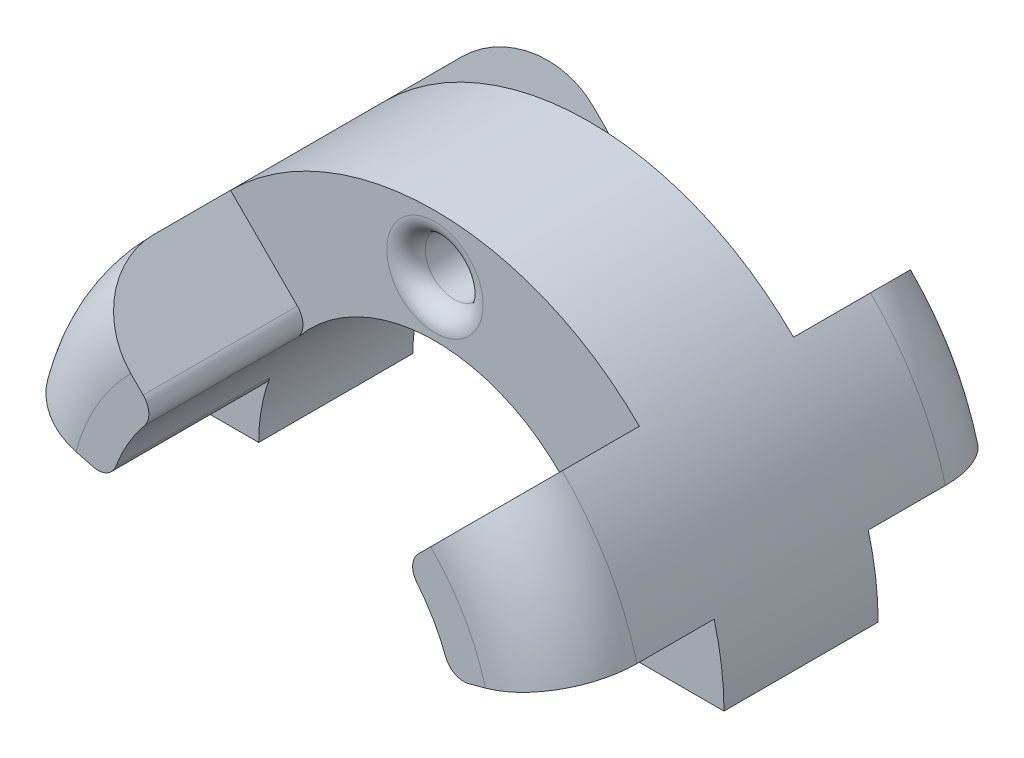
SolidWorks part; units mm, degrees
material "PET"
ref_plane "Front Plane" through (0, 0, 0) normal (0, 0, 1) x (1, 0, 0)
ref_plane "Top Plane" through (0, 0, 0) normal (0, 1, 0) x (1, 0, 0)
ref_plane "Right Plane" through (0, 0, 0) normal (1, 0, 0) x (0, 0, -1)
sketch "Sketch1" plane through (0, 0, 0) normal (0, 0, 1) x (1, 0, 0)
  line L0 (0, 0) -> (0, 2.286) construction
  line L1 (0, 2.625) -> (0, 3) construction
  line L2 (0, 2.625) -> (0, 2.286) construction
  circle A0 centre (0, 0) radius 2.286
  circle A1 centre (0, 0) radius 3.75
  circle A2 centre (0, 3) radius 0.375
  circle A3 centre (2.5981, -1.5) radius 0.375
  circle A4 centre (-2.5981, -1.5) radius 0.375
  point P15 (0, 0)
  dimension "D1" = 4.572
  dimension "D2" = 0.75
  dimension "D4" = 7.5
  dimension "D3" = 3
  dimension "D5" = 3
extrude "Boss-Extrude1" add sketch "Sketch1" along normal blind 2
sketch "Sketch2" plane through (0, 0, 2) normal (0, 0, 1) x (1, 0, 0)
  line L0 (-0.5917, -2.2081) -> (-0.9706, -3.6222)
  line L1 (0, 0) -> (0, -4.001) construction
  line L2 (0.5917, -2.2081) -> (0.9706, -3.6222)
  line L3 (-1.6164, 1.6164) -> (-2.6517, 2.6517)
  line L4 (-2.2081, 0.5917) -> (-3.6222, 0.9706)
  line L5 (2.2081, 0.5917) -> (3.6222, 0.9706)
  line L6 (1.6164, 1.6164) -> (2.6517, 2.6517)
  circle A0 centre (0, 0) radius 3.75 construction
  arc A1 (-0.9706, -3.6222) -> (0.9706, -3.6222) centre (0, 0) ccw
  arc A3 (-0.5917, -2.2081) -> (0.5917, -2.2081) centre (0, 0) ccw
  circle A4 centre (0, 0) radius 2.286 construction
  arc A5 (-2.6517, 2.6517) -> (-3.6222, 0.9706) centre (0, 0) ccw
  arc A6 (-1.6164, 1.6164) -> (-2.2081, 0.5917) centre (0, 0) ccw
  arc A7 (3.6222, 0.9706) -> (2.6517, 2.6517) centre (0, 0) ccw
  arc A8 (2.2081, 0.5917) -> (1.6164, 1.6164) centre (0, 0) ccw
  point P20 (0, 0)
  dimension "D1" = 15
  dimension "D2" = 3
extrude "Boss-Extrude2" add sketch "Sketch2" along normal blind 2 and the other way blind 4
fillet "Fillet1" radius 1 6 edges at (0, -3.75, -2) (-3.2476, 1.875, -2) (3.2476, 1.875, -2) (-3.2476, 1.875, 4) (0, -3.75, 4) (3.2476, 1.875, 4)
fillet "Fillet2" radius 0.25 6 edges at (0.375, 3, 0) (0.375, 3, 2) (2.9731, -1.5, 0) (2.9731, -1.5, 2) (-2.2231, -1.5, 0) (-2.2231, -1.5, 2)
fillet "Fillet3" radius 0.25 12 edges at (-2.2081, 0.5917, -1) (2.2081, 0.5917, -1) (0.5917, -2.2081, -1) (-0.5917, -2.2081, -1) (0.5917, -2.2081, 3) (-0.5917, -2.2081, 3) (-1.6164, 1.6164, -1) (1.6164, 1.6164, -1) (1.6164, 1.6164, 3) (2.2081, 0.5917, 3) (-1.6164, 1.6164, 3) (-2.2081, 0.5917, 3)
sketch "Sketch4" plane through (0, 0, 0) normal (0, 0, 1) x (1, 0, 0)
  line L1 (-3.75, 0) -> (3.75, 0)
  line L2 (-3.75, 0) -> (-3.75, -3.75)
  line L3 (-3.75, -3.75) -> (3.75, -3.75)
  line L4 (3.75, 0) -> (3.75, -3.75)
  arc A0 (-3.6222, 0.9706) -> (-0.9706, -3.6222) centre (0, 0) ccw construction
  arc A1 (0.9706, -3.6222) -> (3.6222, 0.9706) centre (0, 0) ccw construction
  arc A2 (-0.9706, -3.6222) -> (0.9706, -3.6222) centre (0, 0) ccw construction
extrude "Cut-Extrude1" cut sketch "Sketch4" against normal through all and the other way through all
sketch "Sketch5" plane through (0, 0, 0) normal (0, -1, 0) x (1, 0, 0)
  line L0 (-3.018, 2) -> (-3.018, 0) construction
  line L1 (-2.286, 2) -> (-3.75, 2) construction
  line L2 (-2.286, 0) -> (-3.75, 0) construction
  line L3 (-3.018, 0) -> (0, 0) construction
  line L4 (0, 0) -> (0, 2) construction
  line L5 (1.7679, 2) -> (-1.7679, 2) construction
  circle A0 centre (-3.018, 1) radius 0.4
  circle A1 centre (3.018, 1) radius 0.4
  dimension "D1" = 0.8
extrude "Cut-Extrude2" cut sketch "Sketch5" against normal blind 0.75
